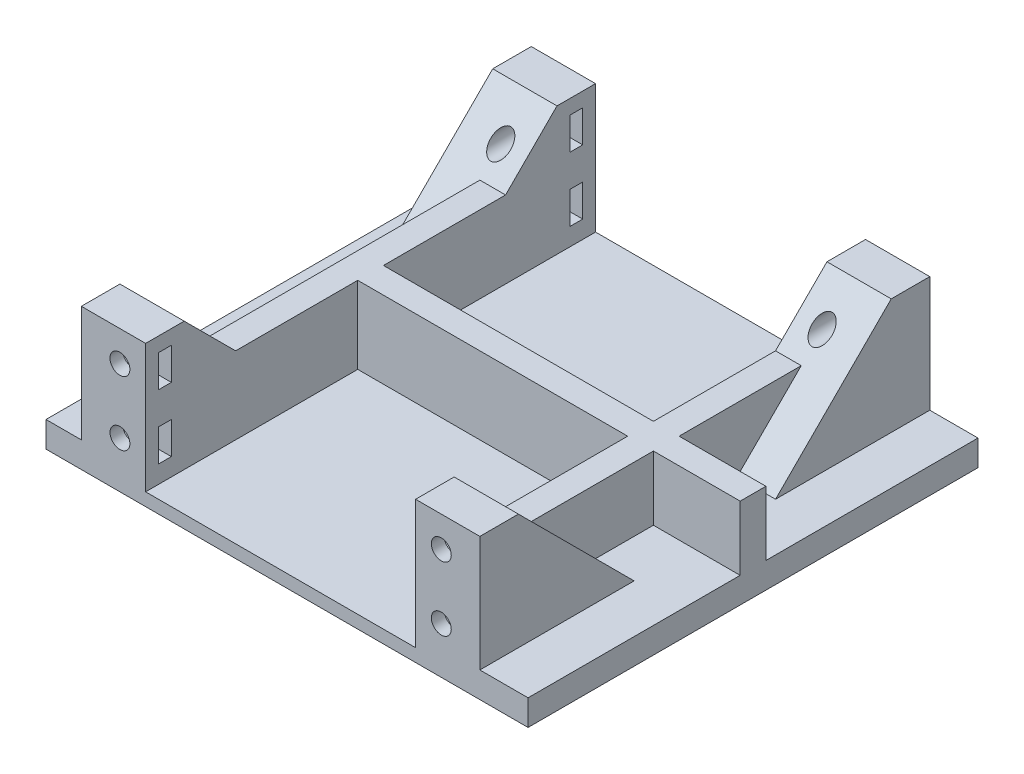
SolidWorks part; units mm, degrees
ref_plane "Front Plane" through (0, 0, 0) normal (0, 0, 1) x (1, 0, 0)
ref_plane "Top Plane" through (0, 0, 0) normal (0, 1, 0) x (1, 0, 0)
ref_plane "Right Plane" through (0, 0, 0) normal (1, 0, 0) x (0, 0, -1)
sketch "Sketch1" plane through (0, 0, 0) normal (0, 1, 0) x (1, 0, 0)
  line L1 (37.5, 35) -> (-37.5, 35)
  line L2 (37.5, 35) -> (37.5, -35)
  line L3 (37.5, -35) -> (-37.5, -35)
  line L4 (-37.5, 35) -> (-37.5, -35)
  line L5 (37.5, 35) -> (-37.5, -35) construction
  line L6 (37.5, -35) -> (-37.5, 35) construction
  point P0 (0, 0)
  dimension "D1" = 70
  dimension "D2" = 75
extrude "Boss-Extrude1" add sketch "Sketch1" along normal blind 4
ref_plane "Plane1" through (20, 0, 0) normal (1, 0, 0) x (0, 0, -1)
ref_plane "Plane2" through (-1, 0, 0) normal (1, 0, 0) x (0, 0, -1)
sketch "Sketch2" plane through (20, 0, 0) normal (1, 0, 0) x (0, 0, -1)
  line L0 (-35, 4) -> (-35, 22)
  line L1 (-35, 22) -> (-29, 22)
  line L2 (-29, 22) -> (-11, 4)
  line L3 (-11, 4) -> (-35, 4)
  line L4 (-35, 4) -> (35, 4) construction
  dimension "D1" = 6
  dimension "D2" = 18
  dimension "D3" = 45
extrude "Boss-Extrude2" add sketch "Sketch2" along normal blind 10
sketch "Sketch4" plane through (0, 4, 0) normal (0, 1, 0) x (1, 0, 0)
  line L0 (-1, -3.3) -> (-1, 3.3) construction
  line L1 (20, -35) -> (-1, -35)
  line L2 (20, -35) -> (20, 0)
  line L3 (20, 0) -> (-1, 0)
  line L4 (-1, -35) -> (-1, 0)
  line L5 (37.5, -35) -> (37.5, 35) construction
  point P9 (37.5, 0)
extrude "Cut-Extrude1" cut sketch "Sketch4" against normal blind 2
sketch "Sketch6" plane through (0, 0, 35) normal (0, 0, 1) x (1, 0, 0)
  line L0 (24, 22) -> (24, 2) construction
  line L1 (30, 22) -> (20, 22) construction
  line L2 (20, 2) -> (24, 2) construction
  line L4 (-1, -3.3) -> (-1, 3.3) construction
  circle A0 centre (24, 7.25) radius 1.55
  circle A1 centre (24, 17.25) radius 1.55
  point P12 (6.6074, 15.6732)
  dimension "D4" = 3.1
  dimension "D1" = 10
  dimension "D2" = 5.25
  dimension "D3" = 25
extrude "Cut-Extrude2" cut sketch "Sketch6" against normal blind 13
sketch "Sketch8" plane through (20, 0, 0) normal (-1, 0, 0) x (0, 0, 1)
  line L0 (35, 17.25) -> (24.25, 17.25) construction
  line L1 (35, 22) -> (35, 2) construction
  line L2 (11, 4) -> (29, 22) construction
  line L3 (35, 7.25) -> (14.25, 7.25) construction
  line L4 (35, 15.7) -> (35, 18.8) construction
  line L5 (35, 5.7) -> (35, 8.8) construction
  line L6 (29, 22) -> (35, 22) construction
  line L7 (33, 19.75) -> (31, 19.75)
  line L8 (33, 19.75) -> (33, 14.75)
  line L9 (33, 14.75) -> (31, 14.75)
  line L10 (31, 19.75) -> (31, 14.75)
  line L11 (33, 19.75) -> (31, 14.75) construction
  line L12 (33, 14.75) -> (31, 19.75) construction
  line L13 (33, 9.75) -> (31, 9.75)
  line L14 (33, 9.75) -> (33, 4.75)
  line L15 (33, 4.75) -> (31, 4.75)
  line L16 (31, 9.75) -> (31, 4.75)
  line L17 (33, 9.75) -> (31, 4.75) construction
  line L18 (33, 4.75) -> (31, 9.75) construction
  point P12 (32, 17.25)
  point P17 (32, 7.25)
  point P24 (32, 22)
  dimension "D1" = 2
  dimension "D2" = 5
extrude "Cut-Extrude4" cut sketch "Sketch8" against normal blind 8
mirror "Mirror1" about plane through (-1, 0, 0) normal (1, 0, 0) of "Cut-Extrude2", "Cut-Extrude4", "Cut-Extrude1", "Boss-Extrude2"
mirror "Mirror2" about plane through (0, 0, 0) normal (0, 0, 1) of "Mirror1", "Cut-Extrude2", "Boss-Extrude2"
sketch "Sketch9" plane through (0, 4, 0) normal (0, 1, 0) x (1, 0, 0)
  line L0 (-37.5, 0) -> (37.5, 0) construction
  line L1 (-37.5, 35) -> (-37.5, -35) construction
  line L2 (37.5, -35) -> (37.5, 35) construction
  line L3 (-22, -21) -> (-22, -2)
  line L4 (-22, -35) -> (-22, 35) construction
  line L5 (-22, -2) -> (20, -2)
  line L6 (37.5, -2) -> (37.5, 2)
  line L7 (-26, 21) -> (-22, 21)
  line L8 (-26, 21) -> (-26, -21)
  line L9 (-26, -21) -> (-22, -21)
  line L10 (24, 2) -> (37.5, 2)
  line L11 (-22, 21) -> (-22, 2)
  line L13 (24, 2) -> (24, 21)
  line L14 (20, -2) -> (20, -21)
  line L15 (20, -21) -> (24, -21)
  line L16 (24, -2) -> (24, -21)
  line L17 (20, -35) -> (20, 35) construction
  line L18 (24, -2) -> (37.5, -2)
  line L19 (20, 21) -> (24, 21)
  line L20 (20, 2) -> (20, 21)
  line L21 (-22, 2) -> (20, 2)
  point P15 (-26, 0)
  dimension "D1" = 2
  dimension "D2" = 4
  dimension "D3" = 21
extrude "Boss-Extrude3" add sketch "Sketch9" along normal blind 10 and the other way up to surface (2 mm away) other way up to face at (-1, 2, 0)
sketch "Sketch13" plane through (0, 0, 0) normal (0, -1, 0) x (1, 0, 0)
  line L0 (-26, -21) -> (-26, 21) construction
  line L1 (-26, 5) -> (-17, 5)
  line L2 (-26, 5) -> (-26, -5)
  line L3 (-26, -5) -> (-17, -5)
  line L4 (-17, 5) -> (-17, -5)
  line L5 (-26, 5) -> (-17, -5) construction
  line L6 (-26, -5) -> (-17, 5) construction
  line L7 (-22, 2) -> (-22, -2) construction
  line L8 (-21.5, 0) -> (34.1225, 0) construction
  line L9 (34.1225, 7.5534) -> (34.1225, 0) construction
  line L10 (34.1225, 0) -> (34.1225, -32.0194) construction
  point P0 (-21.5, 0)
  point P11 (-22, 0)
  point P12 (34.1225, 7.5534)
  point P13 (34.1225, -32.0194)
  dimension "D1" = 10
  dimension "D2" = 9
